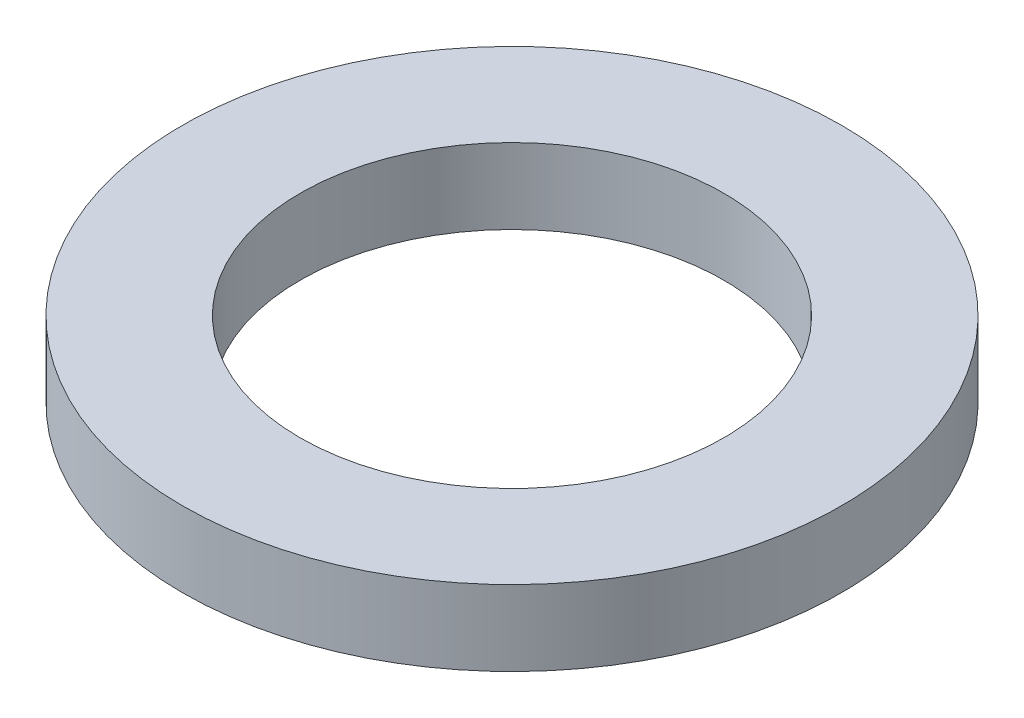
SolidWorks part; units mm, degrees
ref_plane "Front Plane" through (0, 0, 0) normal (0, 0, 1) x (1, 0, 0)
ref_plane "Top Plane" through (0, 0, 0) normal (0, 1, 0) x (1, 0, 0)
ref_plane "Right Plane" through (0, 0, 0) normal (1, 0, 0) x (0, 0, -1)
sketch "BodySke" plane through (0, 0, 0) normal (0, 0, -1) x (1, 0, 0)
  line L0 (0, 0) -> (0, 7.8986) construction
  line L2 (4.5, 1.6) -> (7, 1.6)
  line L3 (4.5, 1.6) -> (4.5, 0)
  line L4 (4.5, 0) -> (7, 0)
  line L5 (7, 1.6) -> (7, 0)
  dimension "Inner_dia" = 9
  dimension "Outer_dia" = 14
  dimension "Thickness" = 1.6
revolve "BaseBody" add sketch "BodySke" angle 360 about L0
